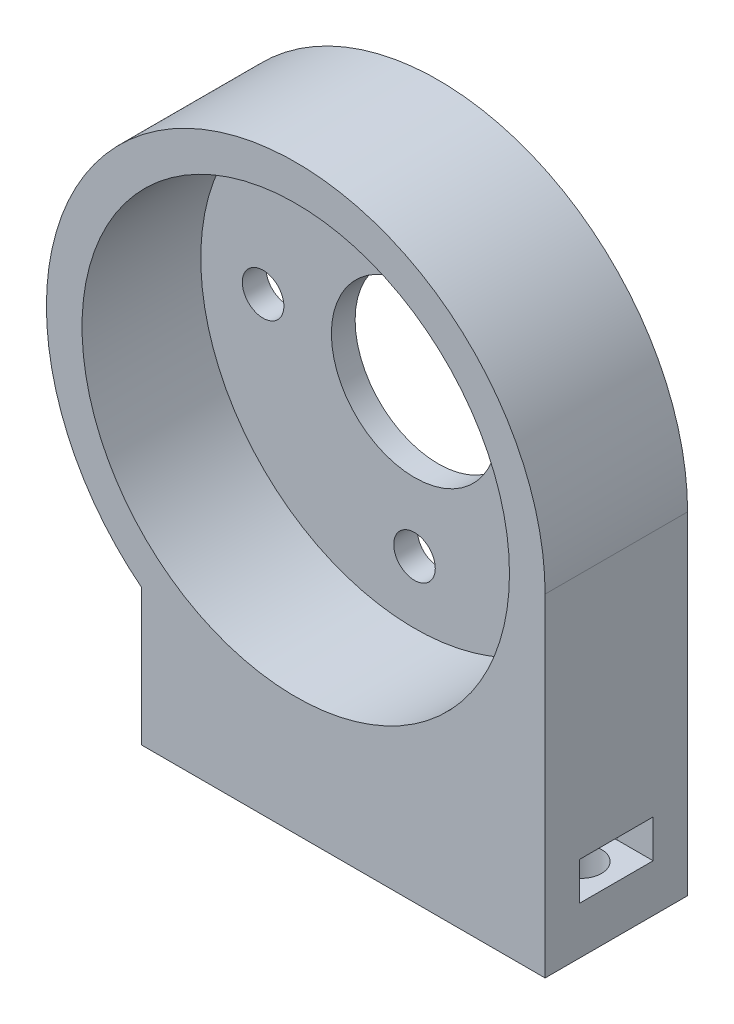
SolidWorks part; units mm, degrees
ref_plane "Alzado" through (0, 0, 0) normal (0, 0, 1) x (1, 0, 0)
ref_plane "Planta" through (0, 0, 0) normal (0, 1, 0) x (1, 0, 0)
ref_plane "Vista lateral" through (0, 0, 0) normal (1, 0, 0) x (0, 0, -1)
sketch "Croquis1" plane through (0, 0, 0) normal (0, 0, 1) x (1, 0, 0)
  line L1 (-13, -28) -> (21, -28)
  line L2 (21, -28) -> (21, 0)
  line L3 (-13, -16.4924) -> (-13, -28)
  circle A0 centre (0, 0) radius 18
  arc A2 (21, 0) -> (-13, -16.4924) centre (0, 0) ccw
  dimension "D1" = 36
  dimension "D2" = 34
  dimension "D3" = 28
extrude "Saliente-Extruir1" add sketch "Croquis1" along normal blind 10
sketch "Croquis2" plane through (0, 0, 10) normal (0, 0, 1) x (1, 0, 0)
  line L0 (21, 0) -> (21, -28)
  line L1 (21, -28) -> (-13, -28)
  line L3 (-13, -28) -> (-13, -16.4924)
  line L4 (0, 12.75) -> (0, -12.75) construction
  line L5 (-12.75, 0) -> (12.75, 0) construction
  circle A0 centre (0, 0) radius 7
  arc A2 (21, 0) -> (-13, -16.4924) centre (0, 0) ccw
  circle A4 centre (0, -12.75) radius 1.75
  circle A5 centre (0, 12.75) radius 1.75
  circle A6 centre (-12.75, 0) radius 1.75
  dimension "D1" = 14
  dimension "D2" = 3.5
  dimension "D3" = 3.5
  dimension "D6" = 3.5
  dimension "D4" = 25.5
  dimension "D5" = 25.5
extrude "Saliente-Extruir2" add sketch "Croquis2" against normal blind 2 from surface starting at face at (0.7087, -11.3379, 0)
sketch "Croquis7" plane through (0, -28, 0) normal (0, -1, 0) x (1, 0, 0)
  line L0 (-21, 4) -> (21, 4) construction
  line L1 (21, 10) -> (21, -2) construction
  line L2 (21, -2) -> (21, 10) construction
  line L4 (-13, 10) -> (-13, -2) construction
  circle A0 centre (-10, 4) radius 1.75
  circle A1 centre (18, 4) radius 1.75
  dimension "D1" = 3.5
  dimension "D2" = 3.5
  dimension "D3" = 3
  dimension "D4" = 3
extrude "Cortar-Extruir3" cut sketch "Croquis7" against normal blind 8
ref_plane "Plano1" through (0, -24, 0) normal (0, -1, 0) x (-1, 0, 0)
sketch "Croquis8" plane through (0, -24, 0) normal (0, -1, 0) x (-1, 0, 0)
  line L0 (-18, -0.9) -> (-21, -0.9)
  line L1 (-21, 2) -> (-21, -10) construction
  line L2 (-18, -7.1) -> (-21, -7.1)
  line L3 (10, -0.9) -> (13, -0.9)
  line L4 (13, 2) -> (13, -10) construction
  line L5 (13, 2) -> (13, -10) construction
  line L6 (10, -7.1) -> (13, -7.1)
  line L7 (13, -0.9) -> (13, -7.1)
  line L10 (-21, -0.9) -> (-21, -7.1)
  arc A0 (-18, -7.1) -> (-18, -0.9) centre (-18, -4) ccw
  arc A1 (10, -0.9) -> (10, -7.1) centre (10, -4) ccw
  dimension "D1" = 6.2
  dimension "D2" = 6.2
extrude "Cortar-Extruir4" cut sketch "Croquis8" against normal blind 3.2
